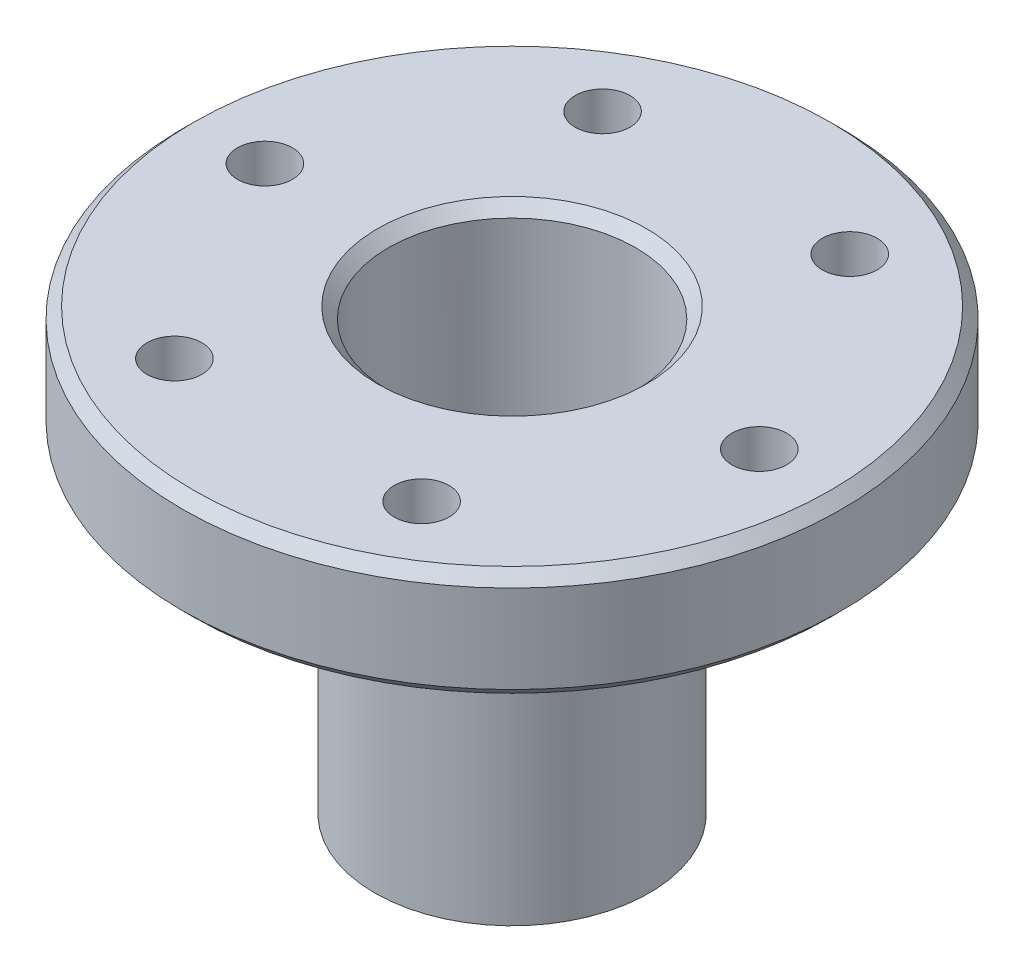
SolidWorks part; units mm, degrees
ref_plane "Front Plane" through (0, 0, 0) normal (0, 0, 1) x (1, 0, 0)
ref_plane "Top Plane" through (0, 0, 0) normal (0, 1, 0) x (1, 0, 0)
ref_plane "Right Plane" through (0, 0, 0) normal (1, 0, 0) x (0, 0, -1)
sketch "Sketch1" plane through (0, 0, 0) normal (0, 1, 0) x (1, 0, 0)
  circle A0 centre (0, 0) radius 22.5
  circle A1 centre (0, 0) radius 60
  circle A2 centre (0, 0) radius 45 construction
  circle A3 centre (45, 0) radius 5
  circle A4 centre (22.5, -38.9711) radius 5
  circle A5 centre (-22.5, -38.9711) radius 5
  circle A6 centre (-45, 0) radius 5
  circle A7 centre (-22.5, 38.9711) radius 5
  circle A8 centre (22.5, 38.9711) radius 5
  point P7 (0, 0)
  point P20 (0, 0)
  dimension "D1" = 120
  dimension "D2" = 45
  dimension "D3" = 90
  dimension "D4" = 10
  dimension "D5" = 45
extrude "Boss-Extrude1" add sketch "Sketch1" along normal blind 20
chamfer "Chamfer1" distance 2 angle 45 3 edges at (0, 0, 60) (0, 20, 22.5) (0, 20, 60)
sketch "Sketch2" plane through (0, 0, 0) normal (0, -1, 0) x (1, 0, 0)
  circle A0 centre (0, 0) radius 25
  circle A1 centre (0, 0) radius 22.5
  dimension "D1" = 50
  dimension "D2" = 45
extrude "Boss-Extrude2" add sketch "Sketch2" along normal blind 60
chamfer "Chamfer2" distance 2 angle 45 1 edges at (0, -60, -22.5)
